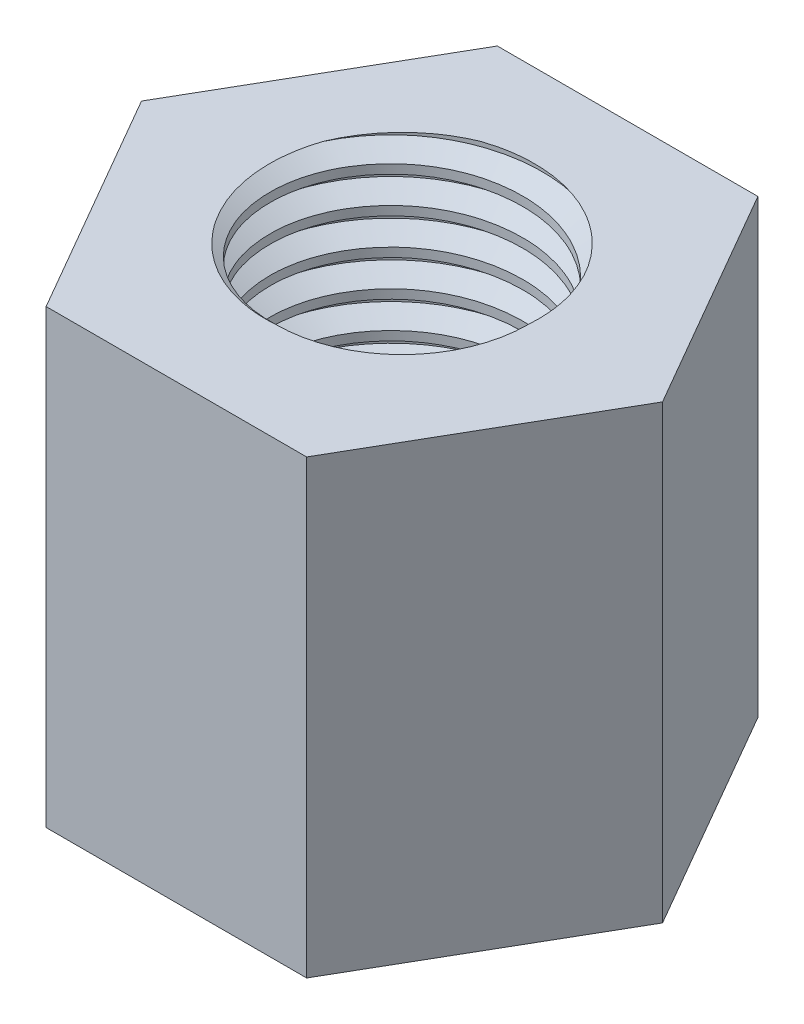
SolidWorks part; units mm, degrees
ref_plane "Front Plane" through (0, 0, 0) normal (0, 0, 1) x (1, 0, 0)
ref_plane "Top Plane" through (0, 0, 0) normal (0, 1, 0) x (1, 0, 0)
ref_plane "Right Plane" through (0, 0, 0) normal (1, 0, 0) x (0, 0, -1)
sketch "Sketch1" plane through (0, 0, 0) normal (0, 1, 0) x (1, 0, 0)
  line L1 (5.7735, 0) -> (2.8868, 5)
  line L2 (2.8868, 5) -> (-2.8868, 5)
  line L3 (-2.8868, 5) -> (-5.7735, 0)
  line L4 (-5.7735, 0) -> (-2.8868, -5)
  line L5 (-2.8868, -5) -> (2.8868, -5)
  line L6 (2.8868, -5) -> (5.7735, 0)
  circle A0 centre (0, 0) radius 2.8
  circle A1 centre (0, 0) radius 5 construction
  dimension "D1" = 5.6
  dimension "D2" = 10
extrude "Boss-Extrude1" add sketch "Sketch1" along normal blind 10
thread "Thread1" pitch 0.8 method cut profile "Thread Profile1" start angle 0, offset 2, length 0, pitch 0.8, diameter 5.6
ref_plane "Plane1" through (-2.8, 12, 0) normal (0, 0, 1) x (-1, 0, 0)
sketch "Thread Profile1" plane through (-2.8, 12, 0) normal (0, 0, 1) x (-1, 0, 0)
  line L0 (0, 0) -> (0, 0.8) construction
  line L1 (0, 0) -> (0.433, 0.25)
  line L2 (0.433, 0.25) -> (0.433, 0.35)
  line L3 (0.433, 0.35) -> (0, 0.6)
  line L4 (0.433, 0.3) -> (0, 0.3) construction
  line L11 (0, 0) -> (0, 0.6)
  point P2 (0, 0)
  dimension "Pitch" = 0.8
  dimension "Profile_Angle" = 60
  dimension "Profile_Land" = 0.1
  dimension "Profile_Height" = 0.433
